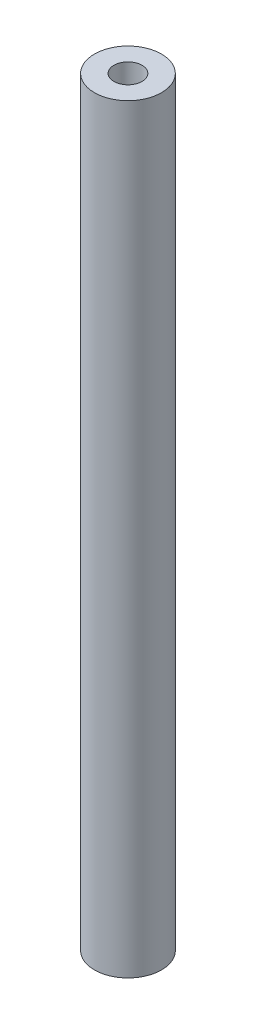
SolidWorks part; units mm, degrees
material "6061-O (SS)"
ref_plane "Alzado" through (0, 0, 0) normal (0, 0, 1) x (1, 0, 0)
ref_plane "Planta" through (0, 0, 0) normal (0, 1, 0) x (1, 0, 0)
ref_plane "Vista lateral" through (0, 0, 0) normal (1, 0, 0) x (0, 0, -1)
sketch "Croquis1" plane through (0, 0, 0) normal (0, 1, 0) x (1, 0, 0)
  circle A0 centre (0, 0) radius 4.7625
  dimension "D1" = 9.525
extrude "Saliente-Extruir1" add sketch "Croquis1" along normal blind 108
ref_plane "Plano1" through (0, 54, 0) normal (0, -1, 0) x (-1, 0, 0)
sketch "Croquis2" plane through (0, 0, 0) normal (0, -1, 0) x (1, 0, 0)
  circle A0 centre (0, 0) radius 2
  dimension "D1" = 4
extrude "Cortar-Extruir1" cut sketch "Croquis2" against normal blind 10
mirror "Simetría1" about plane through (0, 54, 0) normal (0, -1, 0) of "Cortar-Extruir1"
